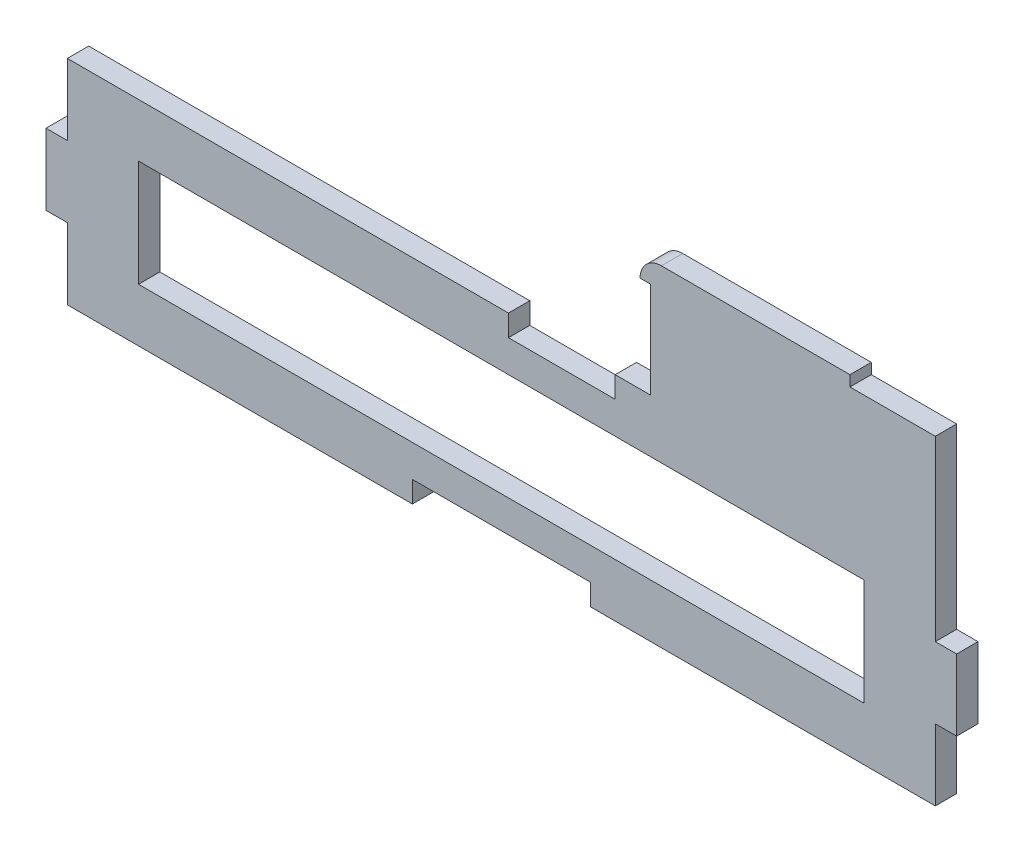
SolidWorks part; units mm, degrees
ref_plane "Спереди" through (0, 0, 0) normal (0, 0, 1) x (1, 0, 0)
ref_plane "Сверху" through (0, 0, 0) normal (0, 1, 0) x (1, 0, 0)
ref_plane "Справа" through (0, 0, 0) normal (1, 0, 0) x (0, 0, -1)
sketch "Эскиз1" plane through (0, 0, 0) normal (0, 0, 1) x (1, 0, 0)
  line L0 (0, 20) -> (0, 0)
  line L1 (0, 0) -> (97, 0)
  line L3 (0, 60) -> (124, 60)
  line L4 (244, 0) -> (244, 54) construction
  line L5 (244, 40) -> (250, 40)
  line L7 (244, 20) -> (250, 20)
  line L8 (250, 40) -> (250, 20)
  line L9 (0, 40) -> (-6, 40)
  line L11 (0, 20) -> (-6, 20)
  line L12 (-6, 40) -> (-6, 20)
  line L13 (0, 60) -> (0, 40)
  line L14 (0, 54) -> (0, 0) construction
  line L15 (244, 0) -> (244, 20)
  line L19 (164, 87) -> (164, 60)
  line L21 (97, 0) -> (97, 6)
  line L22 (20, 15) -> (224, 15)
  line L23 (20, 15) -> (20, 45)
  line L24 (20, 45) -> (224, 45)
  line L25 (224, 15) -> (224, 45)
  line L26 (97, 6) -> (147, 6)
  line L27 (147, 6) -> (147, 0)
  line L28 (147, 0) -> (244, 0)
  line L30 (244, 90) -> (244, 40)
  line L31 (161, 93) -> (220, 93)
  line L34 (164, 87) -> (161, 87)
  line L35 (161, 93) -> (161, 87)
  line L36 (220, 93) -> (220, 90)
  line L37 (220, 90) -> (244, 90)
  line L38 (154, 60) -> (154, 54)
  line L39 (154, 54) -> (124, 54)
  line L40 (124, 54) -> (124, 60)
  line L41 (154, 60) -> (164, 60)
  point P25 (0, 50)
  point P28 (122, 6)
  dimension "D1" = 244
  dimension "D2" = 60
  dimension "D3" = 20
  dimension "D4" = 20
  dimension "D5" = 6
  dimension "D6" = 6
  dimension "D7" = 20
  dimension "D8" = 15
  dimension "D9" = 20
  dimension "D10" = 50
  dimension "D11" = 59
  dimension "D12" = 15
  dimension "D13" = 3
  dimension "D14" = 6
  dimension "D15" = 20
  dimension "D16" = 50
  dimension "D17" = 6
  dimension "D18" = 122
  dimension "D19" = 3
  dimension "D20" = 24
  dimension "D21" = 6
  dimension "D22" = 30
  dimension "D23" = 90
extrude "Бобышка-Вытянуть1" add sketch "Эскиз1" along normal blind 6
fillet "Скругление1" radius 6 1 edges at (161, 93, 3) type face fillet first side face at (161, 90, 3) second side face at (190.5, 93, 3)
